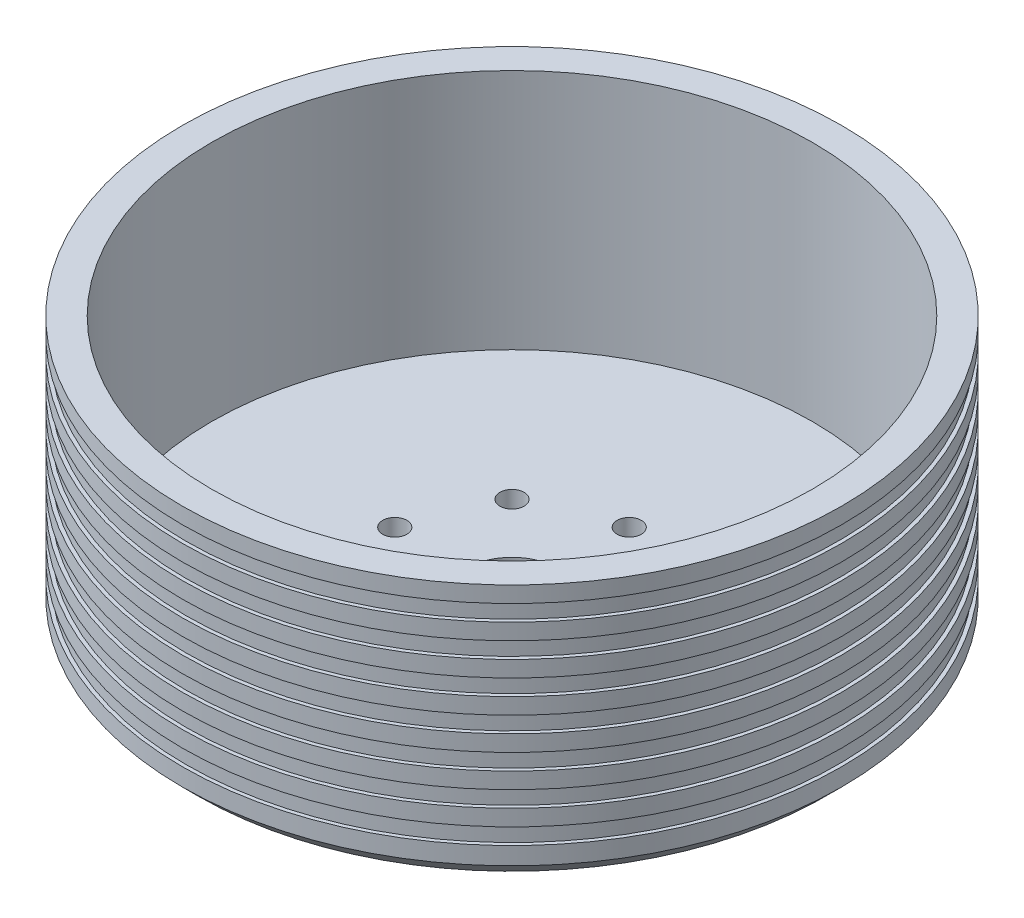
SolidWorks part; units mm, degrees
material "Alumina"
ref_plane "Front Plane" through (0, 0, 0) normal (0, 0, 1) x (1, 0, 0)
ref_plane "Top Plane" through (0, 0, 0) normal (0, 1, 0) x (1, 0, 0)
ref_plane "Right Plane" through (0, 0, 0) normal (1, 0, 0) x (0, 0, -1)
sketch "Sketch1" plane through (0, 0, 0) normal (0, 1, 0) x (1, 0, 0)
  circle A0 centre (0, 0) radius 45
  dimension "D1" = 90
extrude "Boss-Extrude1" add sketch "Sketch1" along normal blind 35.4
sketch "Sketch2" plane through (0, 35.4, 0) normal (0, 1, 0) x (1, 0, 0)
  circle A0 centre (0, 0) radius 41
  dimension "D1" = 82
extrude "Cut-Extrude1" cut sketch "Sketch2" against normal blind 33 contours A0
sketch "Sketch3" plane through (0, 0, 0) normal (0, -1, 0) x (1, 0, 0)
  circle A0 centre (0, 0) radius 29.75
  dimension "D1" = 59.5
extrude "Boss-Extrude2" add sketch "Sketch3" along normal blind 2.5
chamfer "Chamfer1" distance 2.5 angle 45 1 edges at (0, -2.5, -29.75)
sketch "Sketch4" plane through (0, -2.5, 0) normal (0, -1, 0) x (1, 0, 0)
  circle A0 centre (0, 0) radius 6.3
  point P5 (0, 0)
  dimension "D1" = 12.6
extrude "Cut-Extrude2" cut sketch "Sketch4" against normal up to surface (4.9 mm away) up to face at (0, 2.4, 41)
sketch "Sketch5" plane through (0, -2.5, 0) normal (0, -1, 0) x (1, 0, 0)
  circle A0 centre (-16, 0) radius 1.65
  circle A1 centre (-11.3137, 11.3137) radius 1.65
  circle A2 centre (0, 16) radius 1.65
  circle A3 centre (11.3137, 11.3137) radius 1.65
  circle A4 centre (16, 0) radius 1.65
  circle A5 centre (11.3137, -11.3137) radius 1.65
  circle A6 centre (0, -16) radius 1.65
  circle A7 centre (-11.3137, -11.3137) radius 1.65
  point P19 (0, 0)
  dimension "D1" = 3.3
  dimension "D2" = 16
  dimension "D3" = 8
extrude "Cut-Extrude3" cut sketch "Sketch5" against normal up to surface (4.9 mm away) up to face at (0, 2.4, 6.3)
sketch "Sketch7" plane through (0, 0, 0) normal (1, 0, 0) x (0, 0, -1)
  line L0 (-45, 33.2) -> (-44.5, 33.2)
  line L1 (-45, 35.4) -> (-45, 0) construction
  line L2 (-44.5, 33.2) -> (-44.5, 31)
  line L3 (-44.5, 31) -> (-45, 31)
  line L4 (-45, 31) -> (-45, 33.2)
  line L5 (45, 35.4) -> (-45, 35.4) construction
  dimension "D1" = 0.5
  dimension "D2" = 2.2
  dimension "D3" = 2.2
  dimension "D4" = 45
ref_axis "Axis1" through (0, 35.4, 0) along (0, -1, 0)
revolve "Cut-Revolve1" cut sketch "Sketch7" angle 360 about axis through (0, 35.4, 0) along (0, -1, 0)
pattern_linear "LPattern1" count 7 spacing 4.4 along (0, -1, 0) of "Cut-Revolve1"
chamfer "Chamfer2" distance 2.2 angle 45 1 edges at (0, 0, 45)
